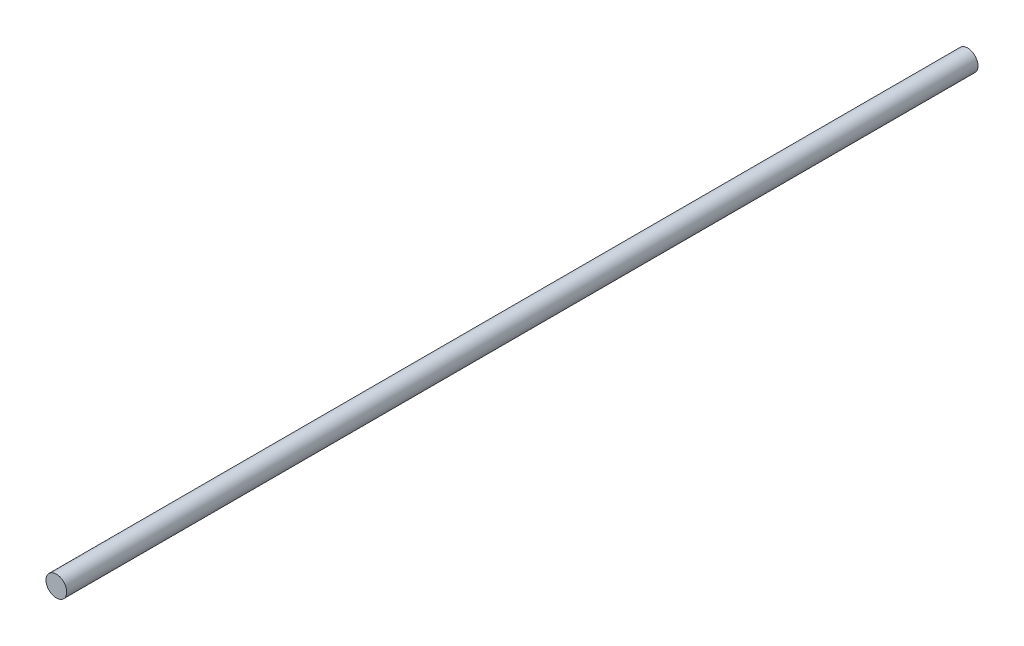
SolidWorks part; units mm, degrees
material "Hexcel AS4C (3000 Filaments)"
ref_plane "Front Plane" through (0, 0, 0) normal (0, 0, 1) x (1, 0, 0)
ref_plane "Top Plane" through (0, 0, 0) normal (0, 1, 0) x (1, 0, 0)
ref_plane "Right Plane" through (0, 0, 0) normal (1, 0, 0) x (0, 0, -1)
sketch "Sketch1" plane through (0, 0, 0) normal (0, 0, 1) x (1, 0, 0)
  circle A0 centre (0, 0) radius 2.5
  dimension "D1" = 5
extrude "Boss-Extrude1" add sketch "Sketch1" along normal blind 220
